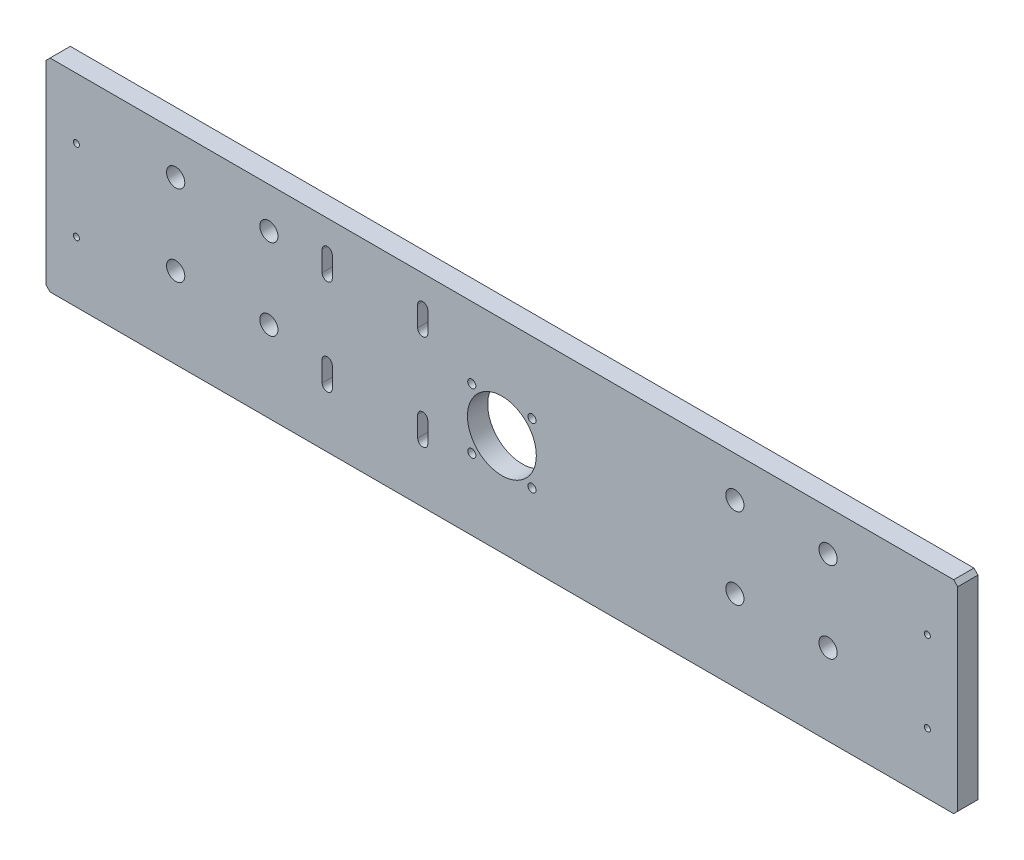
SolidWorks part; units mm, degrees
ref_plane "Piano frontale" through (0, 0, 0) normal (0, 0, 1) x (1, 0, 0)
ref_plane "Piano superiore" through (0, 0, 0) normal (0, 1, 0) x (1, 0, 0)
ref_plane "Piano destro" through (0, 0, 0) normal (1, 0, 0) x (0, 0, -1)
sketch "Schizzo1" plane through (0, 0, 0) normal (0, 0, 1) x (1, 0, 0)
  line L0 (225, 100) -> (225, 0) construction
  line L1 (2, 0) -> (448, 0)
  line L2 (0, 2) -> (0, 98)
  line L3 (2, 100) -> (448, 100)
  line L4 (450, 2) -> (450, 98)
  line L5 (87, 100) -> (87, 0) construction
  line L7 (225, 50) -> (243.5099, 50) construction
  line L9 (225, 50) -> (205.51, 69.49) construction
  line L21 (0, 98) -> (2, 100)
  line L22 (2, 0) -> (0, 2)
  line L23 (448, 0) -> (450, 2)
  line L24 (448, 100) -> (450, 98)
  circle A0 centre (225, 50) radius 17
  circle A1 centre (225, 50) radius 21 construction
  circle A2 centre (239.8492, 64.8492) radius 2
  circle A3 centre (239.8492, 35.1508) radius 2
  circle A4 centre (210.1508, 35.1508) radius 2
  circle A5 centre (386, 40) radius 4.5
  circle A6 centre (386, 80) radius 4.5
  circle A7 centre (340, 40) radius 4.5
  circle A8 centre (340, 80) radius 4.5
  circle A9 centre (435, 70) radius 1.5
  circle A10 centre (435, 30) radius 1.5
  circle A11 centre (15, 30) radius 1.5
  circle A13 centre (210.1508, 64.8492) radius 2
  circle A18 centre (15, 70) radius 1.5
  circle A29 centre (110, 80) radius 4.5
  circle A30 centre (110, 40) radius 4.5
  circle A32 centre (64, 80) radius 4.5
  circle A33 centre (64, 40) radius 4.5
  point P0 (0, 0)
  point P1 (450, 100)
  point P2 (0, 100)
  point P3 (450, 0)
  point P9 (210.1508, 64.8492)
  point P13 (210.1508, 64.8492)
  dimension "D4" = 34
  dimension "D10" = 23
  dimension "D15" = 3
  dimension "D17" = 4
  dimension "D8" = 45
  dimension "D5" = 42
  dimension "D9" = 64
  dimension "D11" = 9
  dimension "D1" = 100
  dimension "D2" = 450
  dimension "D6" = 20
  dimension "D7" = 40
  dimension "D14" = 30
  dimension "D16" = 15
extrude "Boss-Extrude1" add sketch "Schizzo1" against normal blind 10
sketch "Sketch1" plane through (0, 0, -10) normal (0, 0, -1) x (-1, 0, 0)
  line L0 (-185.9381, 80.37) -> (-185.9381, 33.23) construction
  line L1 (-138.7981, 80.37) -> (-138.7981, 33.23) construction
  line L2 (-185.9381, 75.37) -> (-185.9381, 85.37) construction
  line L3 (-188.4381, 75.37) -> (-188.4381, 85.37)
  line L4 (-183.4381, 75.37) -> (-183.4381, 85.37)
  line L5 (-185.9381, 56.8) -> (-138.7981, 56.8) construction
  line L6 (-162.3681, 56.8) -> (-162.3681, 85.2274) construction
  line L7 (-138.7981, 75.37) -> (-138.7981, 85.37) construction
  line L8 (-141.2981, 75.37) -> (-141.2981, 85.37)
  line L9 (-136.2981, 75.37) -> (-136.2981, 85.37)
  line L10 (-185.9381, 28.23) -> (-185.9381, 38.23) construction
  line L11 (-188.4381, 28.23) -> (-188.4381, 38.23)
  line L12 (-183.4381, 28.23) -> (-183.4381, 38.23)
  line L13 (-138.7981, 28.23) -> (-138.7981, 38.23) construction
  line L14 (-141.2981, 28.23) -> (-141.2981, 38.23)
  line L15 (-136.2981, 28.23) -> (-136.2981, 38.23)
  line L17 (0, 2) -> (0, 98) construction
  arc A0 (-188.4381, 75.37) -> (-183.4381, 75.37) centre (-185.9381, 75.37) ccw
  arc A1 (-183.4381, 85.37) -> (-188.4381, 85.37) centre (-185.9381, 85.37) ccw
  arc A2 (-141.2981, 75.37) -> (-136.2981, 75.37) centre (-138.7981, 75.37) ccw
  arc A3 (-136.2981, 85.37) -> (-141.2981, 85.37) centre (-138.7981, 85.37) ccw
  arc A4 (-188.4381, 28.23) -> (-183.4381, 28.23) centre (-185.9381, 28.23) ccw
  arc A5 (-183.4381, 38.23) -> (-188.4381, 38.23) centre (-185.9381, 38.23) ccw
  arc A6 (-141.2981, 28.23) -> (-136.2981, 28.23) centre (-138.7981, 28.23) ccw
  arc A7 (-136.2981, 38.23) -> (-141.2981, 38.23) centre (-138.7981, 38.23) ccw
  point P10 (-185.9381, 80.37)
  point P22 (-138.7981, 80.37)
  point P28 (-185.9381, 33.23)
  point P35 (-138.7981, 33.23)
  dimension "D1" = 10
  dimension "D2" = 5
  dimension "D3" = 5
  dimension "D4" = 5
  dimension "D5" = 5
  dimension "D6" = 138.7981
  dimension "D7" = 185.9381
extrude "Cut-Extrude1" cut sketch "Sketch1" against normal through all
